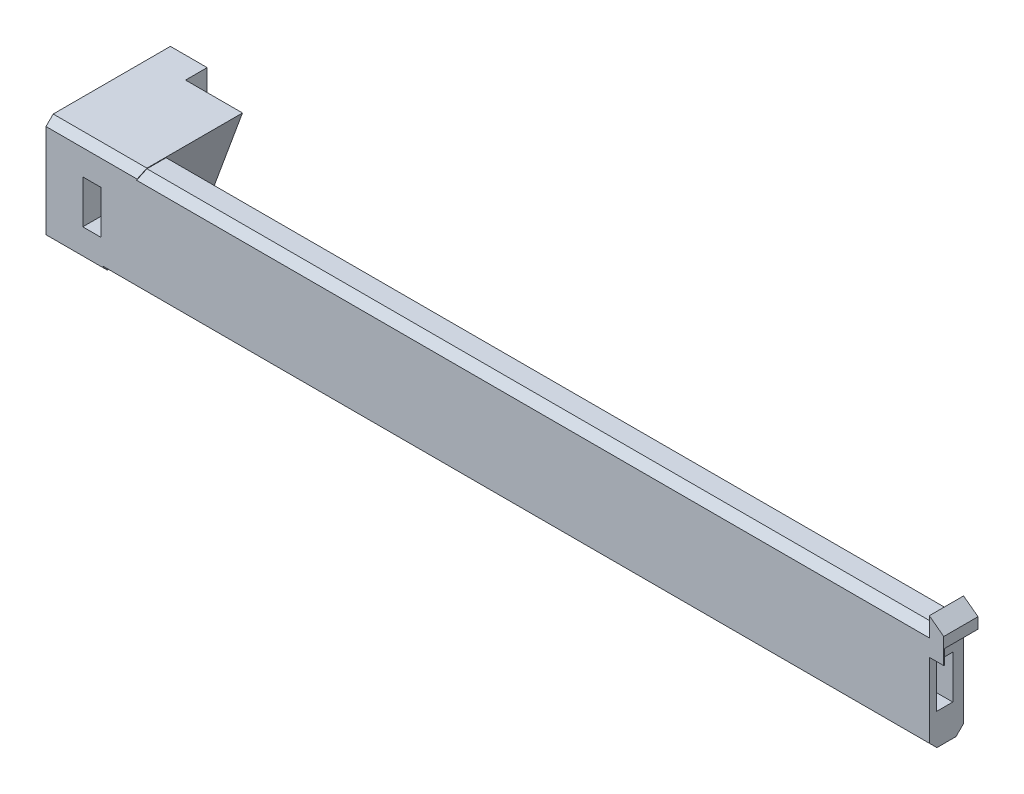
SolidWorks part; units mm, degrees
ref_plane "Front Plane" through (0, 0, 0) normal (0, 0, 1) x (1, 0, 0)
ref_plane "Top Plane" through (0, 0, 0) normal (0, 1, 0) x (1, 0, 0)
ref_plane "Right Plane" through (0, 0, 0) normal (1, 0, 0) x (0, 0, -1)
sketch "Sketch1" plane through (0, 0, 0) normal (0, 0, 1) x (1, 0, 0)
  line L0 (-315, 0) -> (315, 0)
  line L1 (-285.1688, 41.9) -> (-262.5188, 41.9)
  line L2 (-285.1688, 41.9) -> (-285.1688, 21.6)
  line L3 (-285.1688, 21.6) -> (-262.5188, 21.6)
  line L4 (-262.5188, 41.9) -> (-262.5188, 21.6)
  line L5 (262.5187, 41.9) -> (285.1687, 41.9)
  line L6 (262.5187, 41.9) -> (262.5187, 21.6)
  line L7 (262.5187, 21.6) -> (285.1687, 21.6)
  line L8 (285.1687, 41.9) -> (285.1687, 21.6)
  line L9 (-170.8687, 160.7) -> (-148.2188, 160.7)
  line L10 (-170.8687, 160.7) -> (-170.8687, 140.4)
  line L11 (-170.8687, 140.4) -> (-148.2188, 140.4)
  line L12 (-148.2188, 160.7) -> (-148.2188, 140.4)
  line L13 (148.2188, 160.7) -> (170.8688, 160.7)
  line L14 (148.2188, 160.7) -> (148.2188, 140.4)
  line L15 (148.2188, 140.4) -> (170.8688, 140.4)
  line L16 (170.8688, 160.7) -> (170.8688, 140.4)
  line L17 (-273.8438, 31.75) -> (273.8438, 31.75)
  line L18 (-159.5437, 150.55) -> (159.5437, 150.55)
  line L19 (315, 0) -> (315, 30.6)
  line L20 (-248.5188, 79.7) -> (-214.0187, 79.7)
  line L21 (-248.5188, 79.7) -> (-248.5188, 44.9)
  line L22 (-248.5188, 44.9) -> (-214.0187, 44.9)
  line L23 (-214.0187, 79.7) -> (-214.0187, 44.9)
  line L24 (-189.0187, 88.6) -> (-129.3687, 88.6)
  line L25 (-189.0187, 88.6) -> (-189.0187, 48.9)
  line L26 (-189.0187, 48.9) -> (-129.3687, 48.9)
  line L27 (-129.3687, 88.6) -> (-129.3687, 48.9)
  line L28 (-8.5687, 81.6) -> (61.1313, 81.6)
  line L29 (-8.5687, 81.6) -> (-8.5687, 46.9)
  line L30 (-8.5687, 46.9) -> (61.1313, 46.9)
  line L31 (61.1313, 81.6) -> (61.1313, 46.9)
  line L32 (315, 30.6) -> (254, 197)
  line L33 (254, 197) -> (-254, 197)
  line L34 (-254, 197) -> (-315, 30.6)
  line L35 (-315, 30.6) -> (-315, 0)
  line L36 (-315, 4.4515) -> (-244.4143, 197)
  circle A0 centre (-273.8438, 31.75) radius 2.05
  circle A1 centre (273.8438, 31.75) radius 2.05
  circle A2 centre (-159.5437, 150.55) radius 2.05
  circle A3 centre (159.5437, 150.55) radius 2.05
  circle A4 centre (-195.5187, 59.9) radius 2.05
  point P6 (0, 0)
  point P7 (-273.8438, 41.9)
  point P9 (-262.5187, 31.75)
  point P18 (273.8438, 41.9)
  point P19 (285.1688, 31.75)
  point P26 (-159.5437, 160.7)
  point P27 (-148.2188, 150.55)
  point P34 (159.5437, 160.7)
  point P35 (170.8687, 150.55)
  point P36 (0, 31.75)
  point P37 (0, 150.55)
  point P57 (0, 197)
  dimension "D3" = 4.1
  dimension "D7" = 4.1
  dimension "D10" = 4.1
  dimension "D13" = 4.1
  dimension "D18" = 4.1
  dimension "D1" = 22.65
  dimension "D2" = 20.3
  dimension "D4" = 630
  dimension "D5" = 22.65
  dimension "D6" = 20.3
  dimension "D8" = 22.65
  dimension "D9" = 20.3
  dimension "D11" = 22.65
  dimension "D12" = 20.3
  dimension "D14" = 547.6875
  dimension "D15" = 31.75
  dimension "D16" = 98.5
  dimension "D17" = 319.0875
  dimension "D19" = 6.5
  dimension "D20" = 69.7
  dimension "D21" = 34.7
  dimension "D22" = 59.65
  dimension "D23" = 39.7
  dimension "D24" = 34.5
  dimension "D25" = 34.8
  dimension "D26" = 14
  dimension "D27" = 3
  dimension "D28" = 25
  dimension "D29" = 4
  dimension "D30" = 11
  dimension "D31" = 120.8
  dimension "D32" = 2
  dimension "D33" = 30.6
  dimension "D34" = 508
  dimension "D35" = 36.3
  dimension "D36" = 197
  dimension "D37" = 9
sketch "Sketch2" plane through (0, 0, 0) normal (0, 0, 1) x (1, 0, 0)
  line L0 (-315, 0) -> (315, 0) construction
  line L1 (-375, 104) -> (375, 104)
  line L2 (-375, 104) -> (-375, 74)
  line L3 (-375, 74) -> (375, 74)
  line L4 (375, 104) -> (375, 74)
  line L6 (-315, 30.6) -> (-315, 0) construction
  line L7 (315, 0) -> (315, 30.6) construction
  dimension "D1" = 74
  dimension "D2" = 30
  dimension "D3" = 60
  dimension "D4" = 60
sketch "Sketch5" plane through (-8.3611, 207.407, 0) normal (0, 0, 1) x (0.7071, 0.7071, 0)
  line L1 (-321.6588, 154.019) -> (-101.6588, 154.019)
  line L2 (-321.6588, 154.019) -> (-321.6588, -65.981)
  line L3 (-321.6588, -65.981) -> (-101.6588, -65.981)
  line L4 (-101.6588, 154.019) -> (-101.6588, -65.981)
  dimension "D1" = 220
  dimension "D2" = 220
sketch "Sketch3" plane through (0, 0, 0) normal (0, 0, 1) x (1, 0, 0)
  line L0 (-148.2188, 160.7) -> (-148.2188, 140.4) construction
  line L1 (-288.1688, 18.6) -> (-145.2188, 18.6)
  line L2 (-288.1688, 18.6) -> (-288.1688, 163.7)
  line L3 (-288.1688, 163.7) -> (-145.2188, 163.7)
  line L4 (-145.2188, 18.6) -> (-145.2188, 163.7)
  line L5 (-170.8687, 160.7) -> (-148.2188, 160.7) construction
  line L6 (-285.1688, 21.6) -> (-262.5188, 21.6) construction
  line L7 (-285.1688, 41.9) -> (-285.1688, 21.6) construction
  line L8 (-288.1688, 18.6) -> (-289.5045, 74)
  line L9 (-315, 4.4515) -> (-244.4143, 197) construction
  line L10 (-375, 74) -> (375, 74) construction
  line L11 (-289.5045, 74) -> (-256.6217, 163.7)
  line L12 (-173.8687, 163.7) -> (-206.6045, 107)
  line L13 (-285.1688, 21.6) -> (-262.5188, 21.6)
  line L14 (-285.1688, 21.6) -> (-285.1688, 41.9)
  line L15 (-285.1688, 41.9) -> (-262.5188, 41.9)
  line L16 (-262.5188, 21.6) -> (-262.5188, 41.9)
  line L17 (-148.2188, 160.7) -> (-170.8687, 160.7)
  line L18 (-148.2188, 160.7) -> (-148.2188, 140.4)
  line L19 (-148.2188, 140.4) -> (-170.8687, 140.4)
  line L20 (-170.8687, 160.7) -> (-170.8687, 140.4)
  line L21 (-206.6045, 107) -> (-277.4071, 107)
  line L22 (-375, 104) -> (375, 104) construction
  line L23 (-259.5188, 18.6) -> (-259.5188, 71)
  line L24 (-259.5188, 71) -> (-145.2188, 71)
  line L25 (-259.5188, 71) -> (-289.4321, 71)
  line L26 (-206.6045, 107) -> (-145.2188, 107)
  circle A0 centre (-159.5437, 150.55) radius 2.05
  circle A1 centre (-273.8438, 31.75) radius 2.05
  dimension "D1" = 3
  dimension "D2" = 3
  dimension "D3" = 3
  dimension "D4" = 3
  dimension "D5" = 3
  dimension "D6" = 120
  dimension "D7" = 3
  dimension "D8" = 3
  dimension "D9" = 3
sketch "Sketch6" plane through (0, 0, 0) normal (0, 0, 1) x (1, 0, 0)
  line L0 (-375, 104) -> (375, 104) construction
  line L1 (-69.0901, 104) -> (-299.0901, 104)
  line L2 (-69.0901, 104) -> (-69.0901, 74)
  line L3 (-69.0901, 74) -> (-299.0901, 74)
  line L4 (-299.0901, 104) -> (-299.0901, 74)
  line L5 (-375, 74) -> (375, 74) construction
  line L6 (-254, 197) -> (-315, 30.6) construction
  line L9 (-299.0901, 74) -> (-310.0901, 74)
  line L10 (-299.0901, 74) -> (-299.0901, 104)
  line L11 (-299.0901, 104) -> (-310.0901, 104)
  line L12 (-310.0901, 74) -> (-310.0901, 104)
  dimension "D1" = 230
  dimension "D2" = 11
extrude "Boss-Extrude1" add sketch "Sketch6" along normal blind 9.5 contours L1 L4 L3 L2 region at (-184.0901, 89, 0)
sketch "Sketch9" plane through (-299.0901, 0, 0) normal (-1, 0, 0) x (0, 0, 1)
  line L0 (9.5, 104) -> (9.5, 74) construction
  line L1 (3, 83) -> (7.5, 83)
  line L2 (3, 83) -> (3, 95)
  line L3 (3, 95) -> (7.5, 95)
  line L4 (7.5, 83) -> (7.5, 95)
  line L6 (0, 4.4515) -> (0, 197) construction
  line L7 (9.5, 74) -> (0, 74) construction
  point P7 (9.5, 89)
  point P16 (7.5, 89)
  dimension "D1" = 4.5
  dimension "D2" = 12
  dimension "D3" = 3
sketch "Sketch11" plane through (0, 0, 0) normal (0, 0, 1) x (1, 0, 0)
  line L0 (-299.0901, 74) -> (-288.0925, 104)
  line L1 (-254, 197) -> (-315, 30.6) construction
  line L2 (-375, 104) -> (375, 104) construction
  line L3 (-288.0925, 104) -> (-314.0901, 104)
  line L4 (-314.0901, 104) -> (-314.0901, 74)
  line L5 (-375, 74) -> (375, 74) construction
  line L6 (-314.0901, 74) -> (-299.0901, 74)
  dimension "D1" = 15
extrude "Boss-Extrude2" add sketch "Sketch11" along normal up to surface (9.5 mm away) and the other way blind 25 up to face at (-184.0901, 89, 9.5)
sketch "Sketch12" plane through (-314.0901, 0, 0) normal (-1, 0, 0) x (0, 0, 1)
  line L0 (9.5, 104) -> (9.5, 74) construction
  circle A0 centre (1.5, 89) radius 6.5
  point P5 (9.5, 89)
  dimension "D1" = 13
  dimension "D2" = 8
extrude "Cut-Extrude2" cut sketch "Sketch12" against normal blind 2
sketch "Sketch13" plane through (0, 0, -25) normal (0, 0, -1) x (-1, 0, 0)
  line L0 (314.0901, 104) -> (314.0901, 74) construction
  line L1 (307.6401, 79) -> (307.6401, 99)
  line L2 (303.8901, 74) -> (303.8901, 104)
  line L3 (375, 74) -> (-375, 74) construction
  line L4 (375, 104) -> (-375, 104) construction
  circle A0 centre (307.6401, 79) radius 1.75
  circle A1 centre (307.6401, 99) radius 1.75
  point P4 (309.3901, 79)
  point P7 (307.6401, 89)
  point P8 (314.0901, 89)
  point P15 (305.8901, 79)
  dimension "D1" = 3.5
  dimension "D2" = 20
  dimension "D3" = 6.45
  dimension "D4" = 2
sketch "Sketch15" plane through (0, 0, 0) normal (0, 0, -1) x (-1, 0, 0)
  line L4 (69.0901, 104) -> (69.0901, 74) construction
  circle A0 centre (158.0901, 89) radius 6.5
  point P7 (69.0901, 89)
  dimension "D1" = 13
  dimension "D2" = 89
extrude "Cut-Extrude3" cut sketch "Sketch15" against normal blind 2
sketch "Sketch16" plane through (0, 0, -25) normal (0, 0, -1) x (-1, 0, 0)
  line L0 (303.8901, 74) -> (303.8901, 104)
  line L1 (303.8901, 104) -> (288.0925, 104)
  line L2 (288.0925, 104) -> (299.0901, 74)
  line L3 (299.0901, 74) -> (303.8901, 74)
extrude "Cut-Extrude4" cut sketch "Sketch16" against normal blind 6
sketch "Sketch17" plane through (0, 0, -19) normal (0, 0, -1) x (-1, 0, 0)
  line L0 (303.8901, 74) -> (303.8901, 104) construction
  line L1 (303.8901, 83) -> (298.8901, 83)
  line L2 (303.8901, 83) -> (303.8901, 95)
  line L3 (303.8901, 95) -> (298.8901, 95)
  line L4 (298.8901, 83) -> (298.8901, 95)
  line L6 (299.0901, 83) -> (299.0901, 95) construction
  point P6 (299.0901, 83)
  point P7 (299.0901, 95)
  dimension "D1" = 5
extrude "Cut-Extrude5" cut sketch "Sketch9" against normal through all
extrude "Cut-Extrude6" cut sketch "Sketch17" against normal through all
extrude "Cut-Extrude8" cut sketch "Sketch13" against normal blind 16 contours A0 | A1 region at (-306.4377, 100.2024, -25) region at (-308.8426, 80.2024, -25)
sketch "Sketch19" plane through (-314.0901, 0, 0) normal (-1, 0, 0) x (0, 0, 1)
  line L0 (-9, 80.75) -> (-9, 77.25) construction
  line L1 (-13, 76.2) -> (-16, 76.2)
  line L2 (-13, 76.2) -> (-13, 81.8)
  line L3 (-13, 81.8) -> (-16, 81.8)
  line L4 (-16, 76.2) -> (-16, 81.8)
  line L5 (-16, 96.2) -> (-13, 96.2)
  line L6 (-16, 96.2) -> (-16, 101.8)
  line L7 (-16, 101.8) -> (-13, 101.8)
  line L8 (-13, 96.2) -> (-13, 101.8)
  line L9 (-9, 100.75) -> (-9, 97.25) construction
  line L10 (-25, 104) -> (-25, 74) construction
  point P8 (-9, 79)
  point P9 (-9, 99)
  point P12 (-13, 79)
  point P16 (-13, 99)
  dimension "D1" = 5.6
  dimension "D2" = 3
  dimension "D3" = 9
extrude "Cut-Extrude9" cut sketch "Sketch19" against normal blind 10
sketch "Sketch20" plane through (0, 0, 0) normal (0, 0, -1) x (-1, 0, 0)
  line L0 (69.0901, 104) -> (69.0901, 107)
  line L1 (69.0901, 107) -> (65.0901, 104)
  line L2 (375, 104) -> (-375, 104) construction
  line L3 (65.0901, 104) -> (65.0901, 101)
  line L4 (65.0901, 101) -> (94.0901, 101)
  line L5 (94.0901, 101) -> (94.0901, 104)
  line L6 (94.0901, 104) -> (69.0901, 104)
  line L8 (69.0901, 104) -> (69.0901, 74) construction
  line L10 (94.0901, 101) -> (65.0901, 101)
  line L11 (94.0901, 101) -> (94.0901, 97)
  line L12 (94.0901, 97) -> (65.0901, 97)
  line L13 (65.0901, 101) -> (65.0901, 97)
  point P11 (94.0901, 102.5)
  line M12 (69.0901, 104) -> (69.0901, 74)
  dimension "D1" = 3
  dimension "D2" = 4
  dimension "D3" = 25
  dimension "D4" = 3
  dimension "D5" = 4
extrude "Boss-Extrude3" add sketch "Sketch20" against normal up to surface (9.5 mm away) contours L3 L4 L0 L1 M12 | L4 L13 L12 M12 region at (-67.3124, 103.3333, 0) region at (-67.0901, 99, 0) up to face at (-301.3901, 89, 9.5)
extrude "Cut-Extrude10" cut sketch "Sketch20<3>" against normal offset from surface (9.3 mm away) 0.2 contours L12 L11 L4 M12 | L4 L13 L12 M12 region at (-67.0901, 99, 0) region at (-81.5901, 99, 0) up to face at (-301.3901, 89, 9.5)
sketch "Sketch20<3>" plane through (0, 0, 0) normal (0, 0, -1) x (-1, 0, 0) same geometry as "Sketch20"
sketch "Sketch21" plane through (0, 0, 0) normal (0, 0, -1) x (-1, 0, 0)
  line L0 (288.0925, 104) -> (288.1842, 103.75)
  line L1 (254, 197) -> (315, 30.6) construction
  line L2 (288.1842, 103.75) -> (69.0901, 103.75)
  line L3 (69.0901, 104) -> (69.0901, 74) construction
  line L4 (69.0901, 103.75) -> (69.0901, 104)
  line L5 (69.0901, 104) -> (288.0925, 104)
  line L6 (299.0901, 74) -> (69.0901, 74)
  line L7 (69.0901, 74) -> (69.0901, 74.25)
  line L8 (69.0901, 74.25) -> (298.9985, 74.25)
  line L9 (298.9985, 74.25) -> (299.0901, 74)
  dimension "D1" = 0.25
  dimension "D2" = 0.25
extrude "Cut-Extrude11" cut sketch "Sketch21" against normal through all
chamfer "Chamfer2" distance 2.1 angle 45 4 edges at (-184.0443, 74.25, 9.5) (-178.6372, 103.75, 9.5) (-184.0443, 74.25, 0) (-178.6372, 103.75, 0)
chamfer "Chamfer3" distance 2 angle 45 2 edges at (-306.5901, 74, 9.5) (-301.0913, 104, 9.5)
